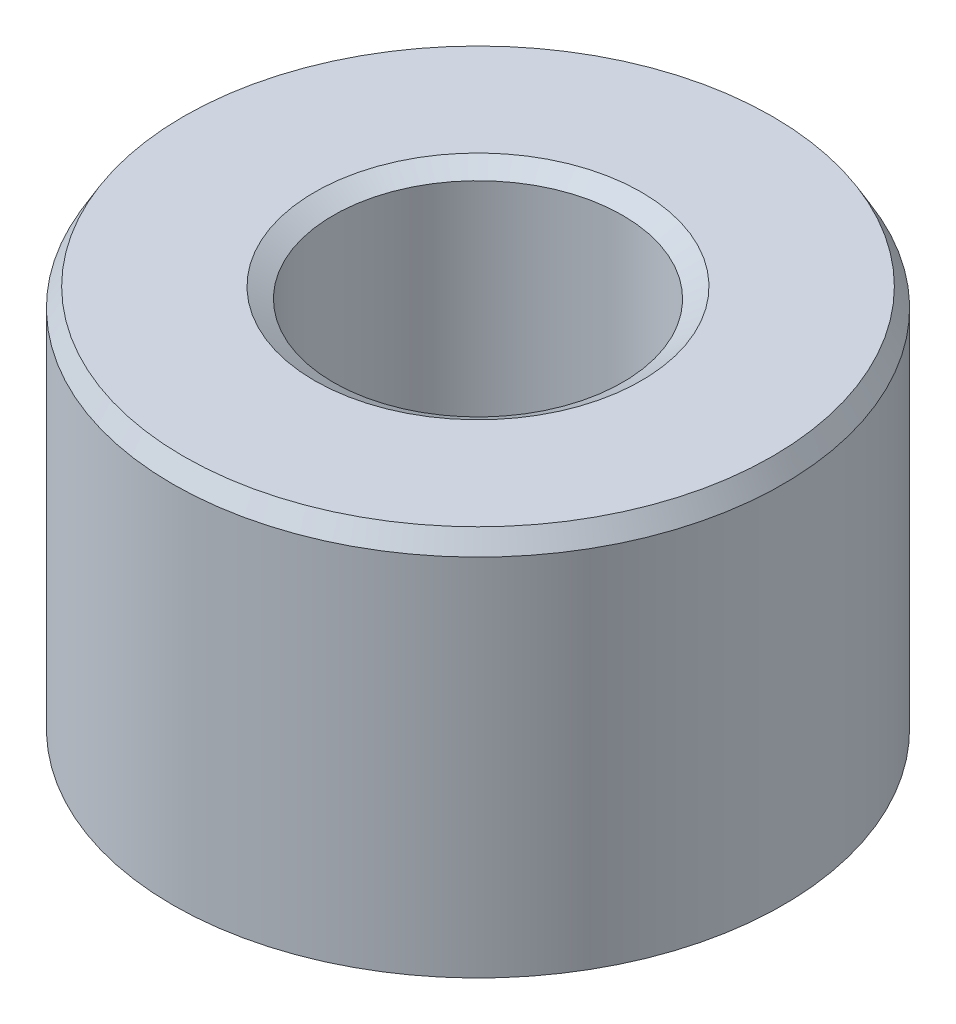
SolidWorks part; units mm, degrees
ref_plane "Front Plane" through (0, 0, 0) normal (0, 0, 1) x (1, 0, 0)
ref_plane "Top Plane" through (0, 0, 0) normal (0, 1, 0) x (1, 0, 0)
ref_plane "Right Plane" through (0, 0, 0) normal (1, 0, 0) x (0, 0, -1)
sketch "Sketch1" plane through (0, 0, 0) normal (0, 1, 0) x (1, 0, 0)
  circle A0 centre (0, 0) radius 45
  dimension "SLEEVE_OD" = 90
extrude "Boss-Extrude1" add sketch "Sketch1" along normal blind 58.0838
sketch "Sketch2" plane through (0, 0, 0) normal (0, 1, 0) x (1, 0, 0)
  circle A0 centre (0, 0) radius 21.3347
  dimension "BORE_D" = 42.6694
extrude "Cut-Extrude1" cut sketch "Sketch2" along normal through all
chamfer "Chamfer1" distance 2.7526 angle 30 4 edges at (0, 58.0838, 21.3347) (0, 0, 21.3347) (0, 0, 45) (0, 58.0838, 45) first distance on face at (0, 58.0838, 21.3347) first distance on face at (0, 0, 21.3347) first distance on face at (0, 58.0838, 45)
